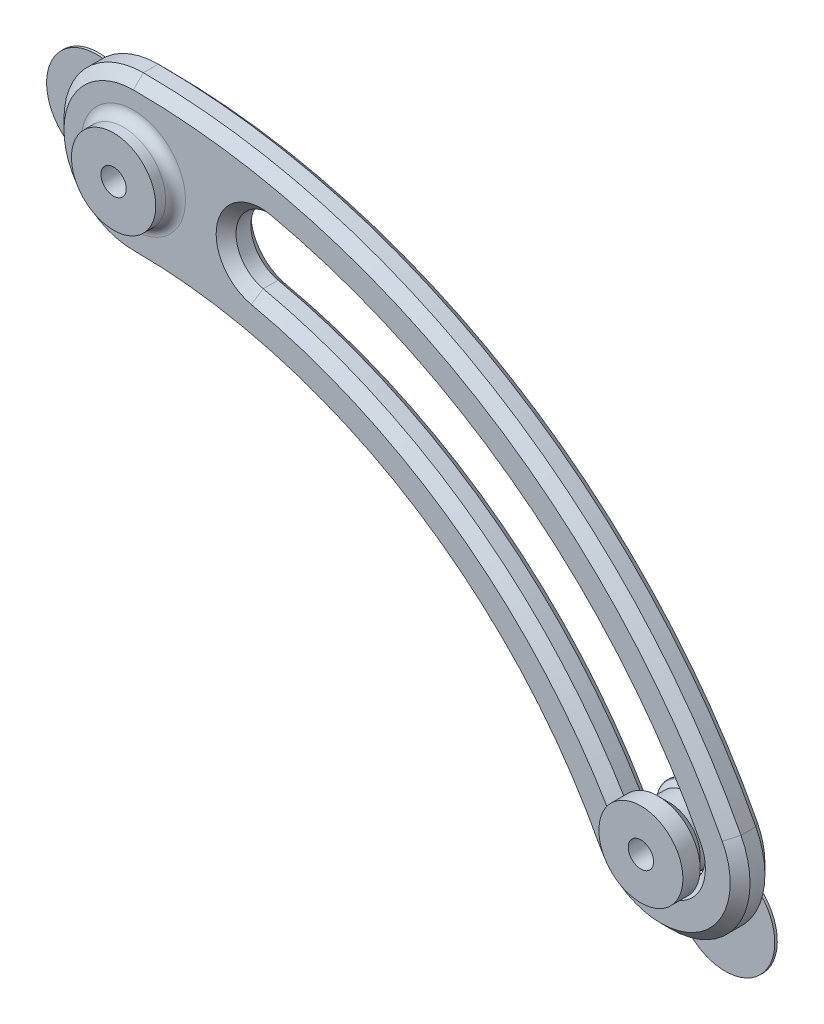
SolidWorks part; units mm, degrees
ref_plane "Front Plane" through (0, 0, 0) normal (0, 0, 1) x (1, 0, 0)
ref_plane "Top Plane" through (0, 0, 0) normal (0, 1, 0) x (1, 0, 0)
ref_plane "Right Plane" through (0, 0, 0) normal (1, 0, 0) x (0, 0, -1)
sketch "Sketch1" plane through (0, 0, 0) normal (0, 0, 1) x (1, 0, 0)
  line L0 (0, 0) -> (0, -120) construction
  line L1 (0, -120) -> (112.7631, -78.9576) construction
  line L4 (25.676, -2.7791) -> (0, -120) construction
  line L5 (106.3006, -64.3208) -> (0, -120) construction
  circle A0 centre (0, 0) radius 2.55
  circle A1 centre (0, 0) radius 8.5
  arc A2 (92.1272, -71.7447) -> (120.474, -56.8969) centre (106.3006, -64.3208) ccw
  arc A3 (0, 16) -> (0, -16) centre (0, 0) ccw
  arc A4 (112.7631, -78.9576) -> (0, 0) centre (0, -120) ccw construction
  arc A5 (100.0998, -67.5687) -> (112.5015, -61.0728) centre (106.3006, -64.3208) ccw
  arc A6 (27.1737, 4.0588) -> (24.1782, -9.617) centre (25.676, -2.7791) ccw
  arc A8 (100.0998, -67.5687) -> (24.1782, -9.617) centre (0, -120) ccw
  arc A9 (112.5015, -61.0728) -> (27.1737, 4.0588) centre (0, -120) ccw
  arc A10 (120.474, -56.8969) -> (0, 16) centre (0, -120) ccw
  arc A11 (92.1272, -71.7447) -> (0, -16) centre (0, -120) ccw
  dimension "D1" = 5.1
  dimension "D2" = 17
  dimension "D3" = 7
  dimension "D4" = 16
  dimension "D5" = 50
  dimension "D6" = 120
  dimension "D7" = 70
extrude "Boss-Extrude1" add sketch "Sketch1" along normal blind 7 contours A11 A2 A10 A3 A1 A9 A5 A8 A6 | A1 A0 region at (-8.2596, 0, 0) region at (56.1772, -23.4396, 0)
extrude "Boss-Extrude2" add sketch "Sketch1<3>" along normal blind 4 from surface contours A1 | A0 starting at face at (55.4925, -28.2895, 7)
sketch "Sketch1<3>" plane through (0, 0, 0) normal (0, 0, 1) x (1, 0, 0) same geometry as "Sketch1"
chamfer "Chamfer1" distance 2 angle 45 16 edges at (-16, 0, 7) (53.8398, -31.0209, 7) (70.4059, -3.6427, 7) (113.7245, -78.4942, 7) (-16, 0, 0) (53.8398, -31.0209, 0) (70.4059, -3.6427, 0) (113.7245, -78.4942, 0) (18.8381, -1.2813, 0) (68.5628, -30.1771, 0) (77.0573, -19.0486, 0) (109.5486, -70.5216, 0) (68.5628, -30.1771, 7) (109.5486, -70.5216, 7) (18.8381, -1.2813, 7) (77.0573, -19.0486, 7)
fillet "Fillet2" radius 2 1 edges at (8.5, 0, 7)
sketch "Sketch2" plane through (0, 0, 11) normal (0, 0, 1) x (1, 0, 0)
  circle A0 centre (0, 0) radius 4.75
  dimension "D1" = 9.5
extrude "Cut-Extrude1" cut sketch "Sketch2" against normal up to surface (11 mm away) from offset 9 contours A0 up to face at (55.7606, -27.8465, 0) offset against normal yes
ref_plane "Plane1" through (49.3228, -94.1652, 0) normal (0.464, -0.8858, 0) x (-0.8858, -0.464, 0)
ref_axis "Axis1" through (106.3006, -64.3208, 5) along (0, 0, -1)
sketch "Sketch3" plane through (49.3228, -94.1652, 0) normal (0.464, -0.8858, 0) x (-0.8858, -0.464, 0)
  line L2 (-73.3208, 0) -> (-71.3208, -2) construction
  line L3 (-57.3208, -2) -> (-55.3208, 0) construction
  line L4 (-57.3208, -5) -> (-57.3208, -2) construction
  line L5 (-55.3208, -7) -> (-57.3208, -5) construction
  line L6 (-64.3208, -5) -> (-64.3208, -2) construction
  line L9 (-57.3208, -2) -> (-55.3208, 0) construction
  line L10 (-57.3208, -5) -> (-57.3208, -2) construction
  line L11 (-55.3208, -7) -> (-57.3208, -5) construction
  line L12 (-55.8511, -7.5303) -> (-58.0708, -5.3107)
  line L13 (-58.0708, -5.3107) -> (-58.0708, -1.6893)
  line L14 (-58.0708, -1.6893) -> (-56.3814, 0)
  line L18 (-56.3814, 0) -> (-64.3208, 0)
  line L20 (-58.0708, -1.6893) -> (-55.8511, 0.5303) construction
  line L21 (-64.3208, -7.5303) -> (-55.8511, -7.5303)
  line L22 (-64.3208, -7.5303) -> (-64.3208, 0)
  dimension "D1" = 0.75
revolve "Revolve1" add sketch "Sketch3" angle 360 about axis through (106.3006, -64.3208, 5) along (0, 0, -1)
chamfer "Chamfer2" distance 0.75 angle 60 1 edges at (114.24, -64.3208, 0) first distance on face at (114.24, -64.3208, 0)
fillet "Fillet3" radius 0.5 1 edges at (113.7096, -64.3208, 0.5303)
sketch "Sketch4" plane through (0, 0, 7.5303) normal (0, 0, 1) x (1, 0, 0)
  circle A1 centre (106.3006, -64.3208) radius 8.4697
  circle A2 centre (106.3006, -64.3208) radius 8.4697
  dimension "D1" = 0
extrude "Boss-Extrude4" add sketch "Sketch4" along normal up to surface (3.4697 mm away) up to face at (8.5, 0, 11)
sketch "Sketch5" plane through (0, 0, 11) normal (0, 0, 1) x (1, 0, 0)
  circle A0 centre (106.3006, -64.3208) radius 2.55
  dimension "D1" = 5.1
extrude "Cut-Extrude2" cut sketch "Sketch5" against normal up to surface (11 mm away) up to face at (99.0337, -64.3208, 0)
sketch "Sketch7" plane through (0, 0, 2) normal (0, 0, -1) x (-1, 0, 0)
  circle A0 centre (0, 0) radius 2.55 construction
  circle A1 centre (0, 0) radius 2.55
extrude "Boss-Extrude5" add sketch "Sketch7" against normal blind 0.5
sketch "Sketch8" plane through (0, 0, 0) normal (0, 0, -1) x (-1, 0, 0)
  arc A0 (10.4286, -9.3405) -> (10.4286, 9.3405) centre (14, 0) ccw
  arc A1 (0, -14) -> (0, 14) centre (0, 0) ccw construction
  arc A2 (-119.4136, -69.2249) -> (-102.8652, -77.8927) centre (-112.7965, -76.7225) ccw
  arc A3 (-118.7024, -57.8249) -> (-93.8989, -70.8167) centre (-106.3006, -64.3208) ccw construction
  arc A4 (-119.4136, -69.2249) -> (-102.8652, -77.8927) centre (-106.3006, -64.3208) ccw
  arc A5 (10.4286, -9.3405) -> (10.4286, 9.3405) centre (0, 0) ccw
  dimension "D1" = 10
  dimension "D2" = 10
extrude "Boss-Extrude6" add sketch "Sketch8" against normal blind 0.5
